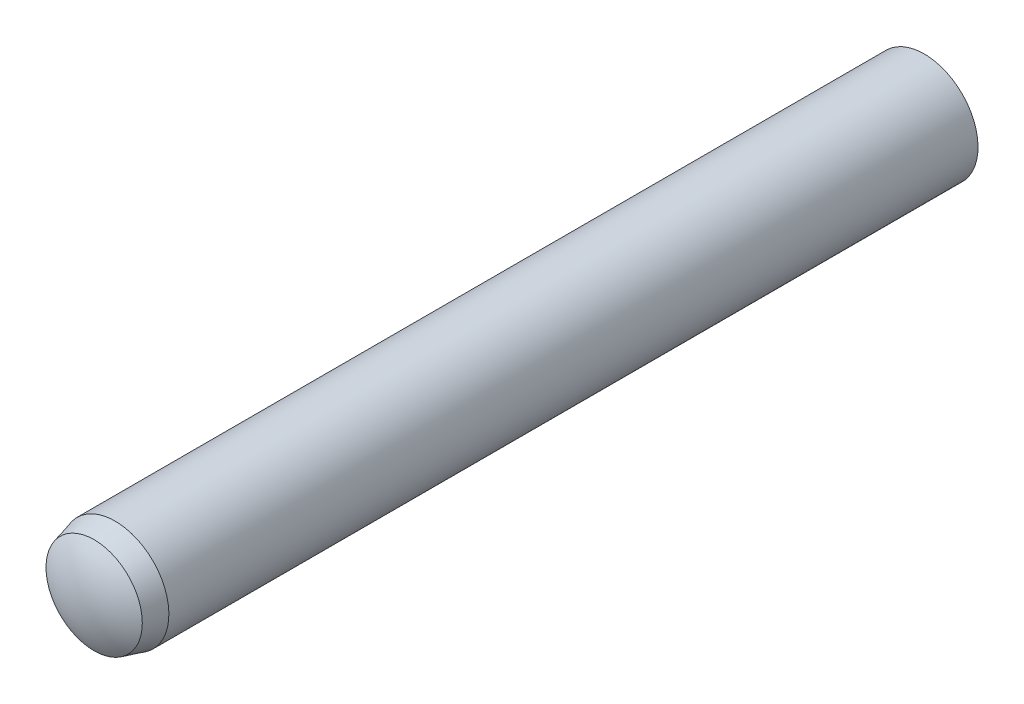
SolidWorks part; units mm, degrees
ref_plane "Front Plane" through (0, 0, 0) normal (0, 0, 1) x (1, 0, 0)
ref_plane "Top Plane" through (0, 0, 0) normal (0, 1, 0) x (1, 0, 0)
ref_plane "Right Plane" through (0, 0, 0) normal (1, 0, 0) x (0, 0, -1)
sketch "Sketch1" plane through (0, 0, 0) normal (0, 0, 1) x (1, 0, 0)
  circle A0 centre (0, 0) radius 1
  point P3 (0, 1)
  dimension "Diameter" = 2
sketch "Sketch2" plane through (0, 0, 0) normal (1, 0, 0) x (0, 0, -1)
  line L0 (-8, 0) -> (8, 0) construction
  line L1 (-8, 0) -> (-8, 1) construction
  line L2 (-8, 1) -> (8, 1)
  line L3 (8, 1) -> (8, 0) construction
  line L4 (-7.74, 0.8955) -> (-7.35, 1)
  arc A0 (-8, 0) -> (-7.74, 0.8955) centre (-6.3278, 0) cw
  arc A1 (8, 0) -> (7.7, 1) centre (6.1833, 0) ccw
  point P2 (0, 0)
  point P11 (-6, 0)
  point P13 (6, 0)
  dimension "D1" = 15
  dimension "D2" = 0.3
  dimension "D3" = 0.65
  dimension "D4" = 0.39
  dimension "D5" = 2
  dimension "D6" = 2
sketch "Sketch3" plane through (0, 0, 0) normal (1, 0, 0) x (0, 0, -1)
  line L0 (-8, 0) -> (8, 0) construction
  line L1 (-7.74, 0.8955) -> (-7.35, 1) construction
  line L2 (-8, 0) -> (8, 0)
  line L3 (-7.74, 0.8955) -> (-7.35, 1)
  line L4 (-7.35, 1) -> (7.7, 1)
  arc A0 (8, 0) -> (7.7, 1) centre (6.1833, 0) ccw construction
  arc A1 (-7.74, 0.8955) -> (-8, 0) centre (-6.3278, 0) ccw construction
  arc A2 (8, 0) -> (7.7, 1) centre (6.1833, 0) ccw
  arc A3 (-7.74, 0.8955) -> (-8, 0) centre (-6.3278, 0) ccw
revolve "Revolve1" add sketch "Sketch3" angle 360 about L2
equation "\"D2@Sketch2\" = \"Diameter@Sketch1\" * .15"
equation "\"D3@Sketch2\" = \"Diameter@Sketch1\" * .325"
equation "\"D4@Sketch2\" = \"D3@Sketch2\" * .6"
equation "\"D5@Sketch2\"=\"Diameter@Sketch1\""
equation "\"D6@Sketch2\"=\"D5@sketch2\""
